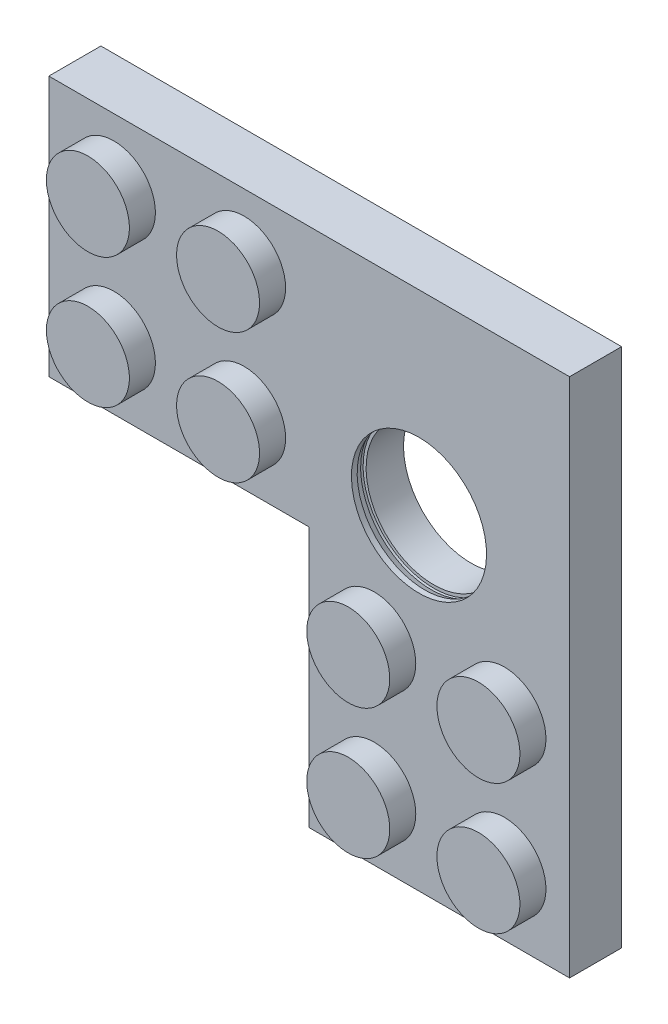
SolidWorks part; units mm, degrees
material "ABS"
ref_plane "Front Plane" through (0, 0, 0) normal (0, 0, 1) x (1, 0, 0)
ref_plane "Top Plane" through (0, 0, 0) normal (0, 1, 0) x (1, 0, 0)
ref_plane "Right Plane" through (0, 0, 0) normal (1, 0, 0) x (0, 0, -1)
sketch "Sketch1" plane through (0, 0, -17.4) normal (0, 0, -1) x (-1, 0, 0)
  line L0 (2.5012, -56.5) -> (18.5012, -56.5) construction
  line L1 (2.5012, -40.5) -> (18.5012, -40.5) construction
  line L2 (18.5012, -56.5) -> (18.5012, -40.5) construction
  line L3 (2.5012, -72.5) -> (2.5012, -56.5) construction
  line L4 (-13.4988, -72.5) -> (-13.4988, -56.5) construction
  line L5 (2.5012, -56.5) -> (18.5012, -56.5) construction
  line L6 (2.5012, -40.5) -> (18.5012, -40.5) construction
  line L7 (18.5012, -56.5) -> (18.5012, -40.5) construction
  line L8 (2.5012, -72.5) -> (2.5012, -56.5) construction
  line L9 (-13.4988, -72.5) -> (-13.4988, -56.5) construction
  line L10 (2.5012, -72.5) -> (-13.4988, -72.5)
  line L11 (-13.4988, -72.5) -> (-13.4988, -40.5)
  line L12 (-13.4988, -40.5) -> (18.5012, -40.5)
  line L13 (18.5012, -40.5) -> (18.5012, -56.5)
  line L14 (18.5012, -56.5) -> (2.5012, -56.5)
  line L15 (2.5012, -56.5) -> (2.5012, -72.5)
  circle A0 centre (-4.2462, -52.5) radius 4 construction
  circle A1 centre (14.5012, -52.5) radius 2.4 construction
  circle A2 centre (14.5012, -44.5) radius 2.4 construction
  circle A3 centre (6.5012, -44.5) radius 2.4 construction
  circle A4 centre (6.5012, -52.5) radius 2.4 construction
  circle A5 centre (-9.4988, -68.5) radius 2.4 construction
  circle A6 centre (-1.4988, -68.5) radius 2.4 construction
  circle A7 centre (-1.4988, -60.5) radius 2.4 construction
  circle A8 centre (-9.4988, -60.5) radius 2.4 construction
  circle A9 centre (-4.2462, -52.5) radius 4 construction
  circle A10 centre (14.5012, -52.5) radius 2.4 construction
  circle A11 centre (14.5012, -44.5) radius 2.4 construction
  circle A12 centre (6.5012, -44.5) radius 2.4 construction
  circle A13 centre (6.5012, -52.5) radius 2.4 construction
  circle A14 centre (-9.4988, -68.5) radius 2.4 construction
  circle A15 centre (-1.4988, -68.5) radius 2.4 construction
  circle A16 centre (-1.4988, -60.5) radius 2.4 construction
  circle A17 centre (-9.4988, -60.5) radius 2.4 construction
  circle A18 centre (-9.4988, -60.5) radius 2.55
  circle A19 centre (-9.4988, -68.5) radius 2.55
  circle A20 centre (-1.4988, -68.5) radius 2.55
  circle A21 centre (-1.4988, -60.5) radius 2.55
  circle A22 centre (6.5012, -52.5) radius 2.55
  circle A23 centre (6.5012, -44.5) radius 2.55
  circle A24 centre (14.5012, -44.5) radius 2.55
  circle A25 centre (14.5012, -52.5) radius 2.55
  circle A26 centre (-4.2462, -52.5) radius 4.15
  dimension "D1" = 0.15
  dimension "D2" = 0.15
extrude "Boss-Extrude1" add sketch "Sketch1" along normal blind 3.2 contours L10 L11 L12 L13 L14 L15 | A26
extrude "Cut-Extrude3" cut sketch "Sketch1<3>" against normal blind 1.8 from surface contours A22 | A23 | A24 | A25 | A18 | A21 | A20 | A19 region at (-6.5012, -52.5, -17.4) region at (-6.5012, -44.5, -17.4) region at (-14.5012, -44.5, -17.4) region at (-14.5012, -52.5, -17.4) starting at face at (-2.5012, -56.5, -20.6)
sketch "Sketch1<3>" plane through (0, 0, -17.4) normal (0, 0, -1) x (-1, 0, 0) same geometry as "Sketch1"
extrude "Boss-Extrude2" add sketch "Sketch1<4>" against normal blind 1.6 contours A23 | A24 | A25 | A22 | A21 | A20 | A18 | A19 region at (-6.5012, -52.5, -17.4) region at (-6.5012, -44.5, -17.4) region at (-14.5012, -44.5, -17.4) region at (-14.5012, -52.5, -17.4)
sketch "Sketch1<4>" plane through (0, 0, -17.4) normal (0, 0, -1) x (-1, 0, 0) same geometry as "Sketch1"
sketch "Sketch2" plane through (4.2462, -52.5, -15.3) normal (-1, 0, 0) x (0, 0, 1)
  line L0 (-2.365, 4) -> (-2.365, 0) construction
  line L1 (-2.9, 4) -> (-2.9, -4) construction
  line L2 (-2.9, 4.235) -> (-2.9, -4.235) construction
  line L3 (-2.365, 4) -> (-2.365, 0) construction
  line L4 (-2.9, 4) -> (-2.9, -4) construction
  line L5 (-2.9, 4.235) -> (-2.9, -4.235) construction
  line L6 (-2.365, 4) -> (-2.9, 4)
  line L7 (-2.9, 4) -> (-2.9, 4.235)
  line L8 (-2.9, 4.235) -> (-2.869, 4.235)
  line L9 (-2.869, 4.235) -> (-2.365, 4)
  line L10 (-2.8468, 4.335) -> (-1.9139, 3.9)
  line L11 (-1.9139, 3.9) -> (-3, 3.9)
  line L12 (-3, 3.9) -> (-3, 4.335)
  line L13 (-3, 4.335) -> (-2.8468, 4.335)
  line L14 (-2.365, 0) -> (49258.1368, 0) construction
  dimension "D1" = 0.1
revolve "Cut-Revolve1" cut sketch "Sketch2" angle 360 about L14
